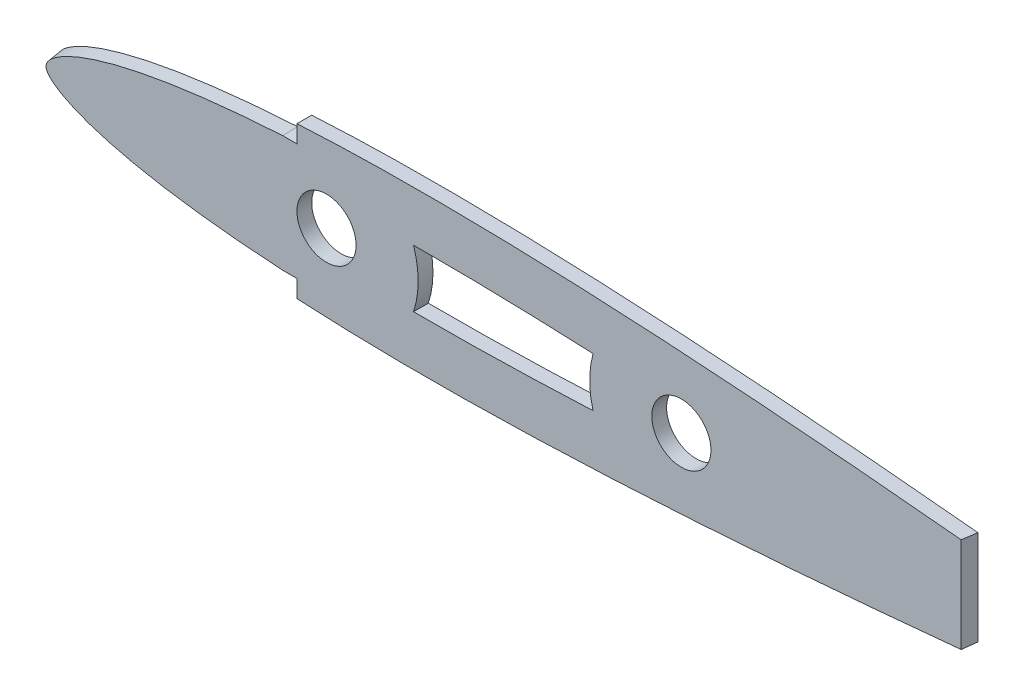
SolidWorks part; units mm, degrees
material "Balsa"
ref_plane "Front Plane" through (0, 0, 0) normal (0, 0, 1) x (1, 0, 0)
ref_plane "Top Plane" through (0, 0, 0) normal (0, 1, 0) x (1, 0, 0)
ref_plane "Right Plane" through (0, 0, 0) normal (1, 0, 0) x (0, 0, -1)
curve "Curve1"
  spline degree 3 poles (283.1769, -0.4783, 0) (283.1769, 0.4783, 0) (282.223, 0.3615, 0) (281.0143, 0.7018, 0) (278.7977, 0.9121, 0) (275.8116, 1.3634, 0) (271.9651, 1.8671, 0) (267.3264, 2.4878, 0) (261.9077, 3.1895, 0) (255.7482, 3.9707, 0) (248.8838, 4.8179, 0) (241.3575, 5.7194, 0) (233.2156, 6.6641, 0) (224.5081, 7.6392, 0) (215.289, 8.6327, 0) (205.6149, 9.6324, 0) (195.5456, 10.6252, 0) (185.1431, 11.5974, 0) (174.4716, 12.536, 0) (163.5969, 13.4255, 0) (152.5858, 14.2512, 0) (141.5064, 14.998, 0) (130.4269, 15.6501, 0) (119.4155, 16.1911, 0) (108.5401, 16.6066, 0) (97.8677, 16.883, 0) (87.464, 17.0069, 0) (77.3931, 16.9683, 0) (67.717, 16.7598, 0) (58.4953, 16.3762, 0) (49.7847, 15.8164, 0) (41.6389, 15.0822, 0) (34.1075, 14.1792, 0) (27.2365, 13.1151, 0) (21.0677, 11.9011, 0) (15.637, 10.5509, 0) (10.9755, 9.0777, 0) (7.1067, 7.4951, 0) (4.043, 5.8139, 0) (1.7891, 4.0308, 0) (0.3455, 2.1026, 0) (-0.161, 0, 0) (0.3455, -2.1026, 0) (1.7891, -4.0308, 0) (4.043, -5.8139, 0) (7.1067, -7.4951, 0) (10.9755, -9.0777, 0) (15.637, -10.5509, 0) (21.0677, -11.9011, 0) (27.2365, -13.1151, 0) (34.1075, -14.1792, 0) (41.6389, -15.0822, 0) (49.7847, -15.8164, 0) (58.4953, -16.3762, 0) (67.717, -16.7598, 0) (77.3931, -16.9683, 0) (87.464, -17.0069, 0) (97.8677, -16.883, 0) (108.5401, -16.6066, 0) (119.4155, -16.1911, 0) (130.4269, -15.6501, 0) (141.5064, -14.998, 0) (152.5858, -14.2512, 0) (163.5969, -13.4255, 0) (174.4716, -12.536, 0) (185.1431, -11.5974, 0) (195.5456, -10.6252, 0) (205.6149, -9.6324, 0) (215.289, -8.6327, 0) (224.5081, -7.6392, 0) (233.2156, -6.6641, 0) (241.3575, -5.7194, 0) (248.8838, -4.8179, 0) (255.7482, -3.9707, 0) (261.9077, -3.1895, 0) (267.3264, -2.4878, 0) (271.9651, -1.8671, 0) (275.8116, -1.3634, 0) (278.7977, -0.9121, 0) (281.0143, -0.7018, 0) (282.223, -0.3615, 0) (283.1769, -0.4783, 0) (283.1769, 0.4783, 0) (282.223, 0.3615, 0) knots -0.004279 -0.001997 -0.001234 0 0.000762 0.003045 0.006832 0.012101 0.018818 0.026939 0.036415 0.047185 0.05918 0.072328 0.086544 0.101741 0.117823 0.134691 0.15224 0.170361 0.188941 0.207865 0.227016 0.246276 0.265525 0.284645 0.30352 0.322035 0.340078 0.357543 0.374325 0.39033 0.405464 0.419644 0.432793 0.444844 0.455738 0.465429 0.473886 0.481102 0.487102 0.491975 0.495931 0.499383 0.502835 0.50679 0.511664 0.517664 0.524879 0.533337 0.543028 0.553922 0.565972 0.579122 0.593302 0.608436 0.62444 0.641223 0.658687 0.676731 0.695245 0.714121 0.733241 0.75249 0.77175 0.7909 0.809825 0.828404 0.846525 0.864074 0.880942 0.897025 0.912222 0.926438 0.939585 0.951581 0.962351 0.971826 0.979948 0.986664 0.991933 0.995721 0.998003 0.998766 1 1.000762 1.003045 1.006832 periodic
sketch "Sketch1" plane through (0, 0, 0) normal (0, 0, 1) x (1, 0, 0)
  spline S0 degree 3 poles (283.1769, -0.4783) (283.1769, 0.4783) (282.223, 0.3615) (281.0143, 0.7018) (278.7977, 0.9121) (275.8116, 1.3634) (271.9651, 1.8671) (267.3264, 2.4878) (261.9077, 3.1895) (255.7482, 3.9707) (248.8838, 4.8179) (241.3575, 5.7194) (233.2156, 6.6641) (224.5081, 7.6392) (215.289, 8.6327) (205.6149, 9.6324) (195.5456, 10.6252) (185.1431, 11.5974) (174.4716, 12.536) (163.5969, 13.4255) (152.5858, 14.2512) (141.5064, 14.998) (130.4269, 15.6501) (119.4155, 16.1911) (108.5401, 16.6066) (97.8677, 16.883) (87.464, 17.0069) (77.3931, 16.9683) (67.717, 16.7598) (58.4953, 16.3762) (49.7847, 15.8164) (41.6389, 15.0822) (34.1075, 14.1792) (27.2365, 13.1151) (21.0677, 11.9011) (15.637, 10.5509) (10.9755, 9.0777) (7.1067, 7.4951) (4.043, 5.8139) (1.7891, 4.0308) (0.3455, 2.1026) (-0.161, 0) (0.3455, -2.1026) (1.7891, -4.0308) (4.043, -5.8139) (7.1067, -7.4951) (10.9755, -9.0777) (15.637, -10.5509) (21.0677, -11.9011) (27.2365, -13.1151) (34.1075, -14.1792) (41.6389, -15.0822) (49.7847, -15.8164) (58.4953, -16.3762) (67.717, -16.7598) (77.3931, -16.9683) (87.464, -17.0069) (97.8677, -16.883) (108.5401, -16.6066) (119.4155, -16.1911) (130.4269, -15.6501) (141.5064, -14.998) (152.5858, -14.2512) (163.5969, -13.4255) (174.4716, -12.536) (185.1431, -11.5974) (195.5456, -10.6252) (205.6149, -9.6324) (215.289, -8.6327) (224.5081, -7.6392) (233.2156, -6.6641) (241.3575, -5.7194) (248.8838, -4.8179) (255.7482, -3.9707) (261.9077, -3.1895) (267.3264, -2.4878) (271.9651, -1.8671) (275.8116, -1.3634) (278.7977, -0.9121) (281.0143, -0.7018) (282.223, -0.3615) (283.1769, -0.4783) (283.1769, 0.4783) (282.223, 0.3615) knots -0.004279 -0.001997 -0.001234 0 0.000762 0.003045 0.006832 0.012101 0.018818 0.026939 0.036415 0.047185 0.05918 0.072328 0.086544 0.101741 0.117823 0.134691 0.15224 0.170361 0.188941 0.207865 0.227016 0.246276 0.265525 0.284645 0.30352 0.322035 0.340078 0.357543 0.374325 0.39033 0.405464 0.419644 0.432793 0.444844 0.455738 0.465429 0.473886 0.481102 0.487102 0.491975 0.495931 0.499383 0.502835 0.50679 0.511664 0.517664 0.524879 0.533337 0.543028 0.553922 0.565972 0.579122 0.593302 0.608436 0.62444 0.641223 0.658687 0.676731 0.695245 0.714121 0.733241 0.75249 0.77175 0.7909 0.809825 0.828404 0.846525 0.864074 0.880942 0.897025 0.912222 0.926438 0.939585 0.951581 0.962351 0.971826 0.979948 0.986664 0.991933 0.995721 0.998003 0.998766 1 1.000762 1.003045 1.006832 only from (283.0068, 0.3566) to (283.0068, 0.3566) construction
  spline S1 degree 3 poles (283.1769, -0.4783) (283.1769, 0.4783) (282.223, 0.3615) (281.0143, 0.7018) (278.7977, 0.9121) (275.8116, 1.3634) (271.9651, 1.8671) (267.3264, 2.4878) (261.9077, 3.1895) (255.7482, 3.9707) (248.8838, 4.8179) (241.3575, 5.7194) (233.2156, 6.6641) (224.5081, 7.6392) (215.289, 8.6327) (205.6149, 9.6324) (195.5456, 10.6252) (185.1431, 11.5974) (174.4716, 12.536) (163.5969, 13.4255) (152.5858, 14.2512) (141.5064, 14.998) (130.4269, 15.6501) (119.4155, 16.1911) (108.5401, 16.6066) (97.8677, 16.883) (87.464, 17.0069) (77.3931, 16.9683) (67.717, 16.7598) (58.4953, 16.3762) (49.7847, 15.8164) (41.6389, 15.0822) (34.1075, 14.1792) (27.2365, 13.1151) (21.0677, 11.9011) (15.637, 10.5509) (10.9755, 9.0777) (7.1067, 7.4951) (4.043, 5.8139) (1.7891, 4.0308) (0.3455, 2.1026) (-0.161, 0) (0.3455, -2.1026) (1.7891, -4.0308) (4.043, -5.8139) (7.1067, -7.4951) (10.9755, -9.0777) (15.637, -10.5509) (21.0677, -11.9011) (27.2365, -13.1151) (34.1075, -14.1792) (41.6389, -15.0822) (49.7847, -15.8164) (58.4953, -16.3762) (67.717, -16.7598) (77.3931, -16.9683) (87.464, -17.0069) (97.8677, -16.883) (108.5401, -16.6066) (119.4155, -16.1911) (130.4269, -15.6501) (141.5064, -14.998) (152.5858, -14.2512) (163.5969, -13.4255) (174.4716, -12.536) (185.1431, -11.5974) (195.5456, -10.6252) (205.6149, -9.6324) (215.289, -8.6327) (224.5081, -7.6392) (233.2156, -6.6641) (241.3575, -5.7194) (248.8838, -4.8179) (255.7482, -3.9707) (261.9077, -3.1895) (267.3264, -2.4878) (271.9651, -1.8671) (275.8116, -1.3634) (278.7977, -0.9121) (281.0143, -0.7018) (282.223, -0.3615) (283.1769, -0.4783) (283.1769, 0.4783) (282.223, 0.3615) knots -0.004279 -0.001997 -0.001234 0 0.000762 0.003045 0.006832 0.012101 0.018818 0.026939 0.036415 0.047185 0.05918 0.072328 0.086544 0.101741 0.117823 0.134691 0.15224 0.170361 0.188941 0.207865 0.227016 0.246276 0.265525 0.284645 0.30352 0.322035 0.340078 0.357543 0.374325 0.39033 0.405464 0.419644 0.432793 0.444844 0.455738 0.465429 0.473886 0.481102 0.487102 0.491975 0.495931 0.499383 0.502835 0.50679 0.511664 0.517664 0.524879 0.533337 0.543028 0.553922 0.565972 0.579122 0.593302 0.608436 0.62444 0.641223 0.658687 0.676731 0.695245 0.714121 0.733241 0.75249 0.77175 0.7909 0.809825 0.828404 0.846525 0.864074 0.880942 0.897025 0.912222 0.926438 0.939585 0.951581 0.962351 0.971826 0.979948 0.986664 0.991933 0.995721 0.998003 0.998766 1 1.000762 1.003045 1.006832 only from (283.0068, 0.3566) to (283.0068, 0.3566)
extrude "Boss-Extrude1" add sketch "Sketch1" along normal blind 3.175
sketch "Sketch2" plane through (0, 0, 3.175) normal (0, 0, 1) x (1, 0, 0)
  circle A0 centre (63.5, 0) radius 6.35
  circle A1 centre (139.7, 0) radius 6.35
  dimension "D1" = 12.7
  dimension "D2" = 12.7
  dimension "D3" = 0
  dimension "D4" = 0
  dimension "D5" = 63.5
  dimension "D6" = 139.7
extrude "Cut-Extrude1" cut sketch "Sketch2" against normal blind 3.175
sketch "Sketch3" plane through (0, 0, 0) normal (0, 1, 0) x (1, 0, 0)
  line L2 (200.2201, 0) -> (199.7735, -3.175)
  line L8 (283.1344, -3.175) -> (283.1344, 0) construction
  line L9 (283.1344, -3.175) -> (283.1344, 0)
  line L10 (199.7735, -3.175) -> (283.1344, -3.175)
extrude "Cut-Extrude2" cut sketch "Sketch3" against normal through all both and the other way through all
sketch "Sketch4" plane through (0, 0, 0) normal (0, 0, -1) x (-1, 0, 0)
  line L0 (-57.15, -15.9311) -> (-57.15, -12.6144)
  line L1 (-57.15, -15.9311) -> (-57.15, -12.6144)
  line L2 (-54.102, -12.6144) -> (-57.15, -12.6144)
  line L3 (-54.102, -12.6144) -> (-57.15, -12.6144)
  line L4 (-57.15, 12.6144) -> (-57.15, 15.9311)
  line L5 (-57.15, 12.6144) -> (-57.15, 15.9311)
  line L6 (-57.15, 12.6144) -> (-54.102, 12.6144)
  line L7 (-57.15, 12.6144) -> (-54.102, 12.6144)
  line L9 (16.291, 29.4613) -> (3.1074, -36.0979)
  line L11 (-57.15, -15.9311) -> (-57.15, -26.911)
  line L12 (-57.15, -26.911) -> (3.1074, -36.0979)
  line L13 (-57.15, 15.9311) -> (-57.15, 23.7689)
  line L14 (-57.15, 23.7689) -> (16.291, 29.4613)
  spline S0 degree 3 poles (1603.9477, 1127.4313) (-409.4491, -100.2252) (-222.7052, 25.2394) (-46.8504, 12.1195) (-43.234, 11.8063) (-39.6271, 11.4462) (-36.0313, 11.0349) (-32.4506, 10.5661) (-28.886, 10.0331) (-25.9367, 9.528) (-23.5902, 9.0821) (-21.8403, 8.725) (-20.101, 8.3428) (-18.3748, 7.9334) (-16.663, 7.4946) (-14.9702, 7.0233) (-13.3008, 6.5163) (-11.6611, 5.9687) (-10.0604, 5.3771) (-8.5083, 4.731) (-7.0229, 4.0237) (-5.6385, 3.2547) (-4.6091, 2.5577) (-3.9035, 1.9678) (-3.4556, 1.5205) (-3.0957, 1.0697) (-2.8713, 0.6793) (-2.7459, 0.308) (-2.7091, 0) (-2.7459, -0.308) (-2.8713, -0.6793) (-3.0958, -1.0697) (-3.4556, -1.5205) (-3.9035, -1.9678) (-4.6094, -2.5579) (-5.6383, -3.2546) (-7.023, -4.0238) (-8.5083, -4.731) (-10.0604, -5.3771) (-11.6611, -5.9687) (-13.3008, -6.5163) (-14.9701, -7.0232) (-16.663, -7.4946) (-18.3748, -7.9334) (-20.101, -8.3428) (-21.8403, -8.725) (-23.5902, -9.0821) (-25.9368, -9.528) (-28.8859, -10.0331) (-32.4506, -10.5661) (-36.0313, -11.0349) (-39.6271, -11.4462) (-43.234, -11.8063) (-46.8504, -12.1195) (-222.1359, -25.197) (-408.2838, 99.3983) (1617.0872, -1107.8528) knots -4.455305 -4.455305 -4.455305 -4.455305 0.03125 0.0625 0.09375 0.125 0.15625 0.1875 0.21875 0.25 0.265625 0.28125 0.296875 0.3125 0.328125 0.34375 0.359375 0.375 0.390625 0.40625 0.421875 0.4375 0.453125 0.460938 0.46875 0.476562 0.484375 0.492188 0.5 0.507812 0.515625 0.523438 0.53125 0.539062 0.546875 0.5625 0.578125 0.59375 0.609375 0.625 0.640625 0.65625 0.671875 0.6875 0.703125 0.71875 0.734375 0.75 0.78125 0.8125 0.84375 0.875 0.90625 0.9375 0.96875 5.440565 5.440565 5.440565 5.440565 only from (-54.102, 12.6144) to (-54.102, -12.6144)
  spline S1 degree 3 poles (-54.102, 12.6144) (-52.893, 12.5437) (-50.4746, 12.3899) (-46.8504, 12.1195) (-43.234, 11.8063) (-39.6271, 11.4462) (-36.0313, 11.0349) (-32.4506, 10.5661) (-28.886, 10.0331) (-25.9367, 9.528) (-23.5902, 9.0821) (-21.8403, 8.725) (-20.101, 8.3428) (-18.3748, 7.9334) (-16.663, 7.4946) (-14.9702, 7.0233) (-13.3008, 6.5163) (-11.6611, 5.9687) (-10.0604, 5.3771) (-8.5083, 4.731) (-7.0229, 4.0237) (-5.6385, 3.2547) (-4.6091, 2.5577) (-3.9035, 1.9678) (-3.4556, 1.5205) (-3.0957, 1.0697) (-2.8713, 0.6793) (-2.7459, 0.308) (-2.7091, 0) (-2.7459, -0.308) (-2.8713, -0.6793) (-3.0958, -1.0697) (-3.4556, -1.5205) (-3.9035, -1.9678) (-4.6094, -2.5579) (-5.6383, -3.2546) (-7.023, -4.0238) (-8.5083, -4.731) (-10.0604, -5.3771) (-11.6611, -5.9687) (-13.3008, -6.5163) (-14.9701, -7.0232) (-16.663, -7.4946) (-18.3748, -7.9334) (-20.101, -8.3428) (-21.8403, -8.725) (-23.5902, -9.0821) (-25.9368, -9.528) (-28.8859, -10.0331) (-32.4506, -10.5661) (-36.0313, -11.0349) (-39.6271, -11.4462) (-43.234, -11.8063) (-46.8504, -12.1195) (-50.4745, -12.3899) (-52.893, -12.5437) (-54.102, -12.6144) knots 0 0 0 0 0.03125 0.0625 0.09375 0.125 0.15625 0.1875 0.21875 0.25 0.265625 0.28125 0.296875 0.3125 0.328125 0.34375 0.359375 0.375 0.390625 0.40625 0.421875 0.4375 0.453125 0.460938 0.46875 0.476562 0.484375 0.492188 0.5 0.507812 0.515625 0.523438 0.53125 0.539062 0.546875 0.5625 0.578125 0.59375 0.609375 0.625 0.640625 0.65625 0.671875 0.6875 0.703125 0.71875 0.734375 0.75 0.78125 0.8125 0.84375 0.875 0.90625 0.9375 0.96875 1 1 1 1
sketch "Sketch5" plane through (0, 0, 3.175) normal (0, 0, 1) x (1, 0, 0)
  line L0 (57.15, -15.8407) -> (57.15, -12.5178)
  line L1 (57.15, -15.8407) -> (57.15, -12.5178)
  line L2 (54.102, -12.5178) -> (57.15, -12.5178)
  line L3 (54.102, -12.5178) -> (57.15, -12.5178)
  line L4 (57.15, 12.5178) -> (57.15, 15.8407)
  line L5 (57.15, 12.5178) -> (57.15, 15.8407)
  line L6 (57.15, 12.5178) -> (54.102, 12.5178)
  line L7 (57.15, 12.5178) -> (54.102, 12.5178)
  line L9 (-13.6603, 32.1968) -> (4.7514, -35.9264)
  line L11 (57.15, 15.8407) -> (57.15, 24.5287)
  line L12 (57.15, 24.5287) -> (-13.6603, 32.1968)
  line L13 (57.15, -15.8407) -> (57.15, -29.0129)
  line L14 (57.15, -29.0129) -> (4.7514, -35.9264)
  spline S0 degree 3 poles (-1613.5734, 1113.0651) (405.921, -99.1234) (220.9953, 25.1428) (46.923, 12.0225) (43.3429, 11.7096) (39.7723, 11.3502) (36.213, 10.9401) (32.6687, 10.4731) (29.1406, 9.9424) (26.2217, 9.4398) (23.8996, 8.9963) (22.1681, 8.6412) (20.4471, 8.2613) (18.7392, 7.8544) (17.0458, 7.4185) (15.3713, 6.9503) (13.7204, 6.447) (12.0991, 5.9036) (10.5167, 5.3168) (8.9829, 4.6764) (7.5154, 3.9756) (6.1484, 3.2144) (5.1324, 2.5254) (4.4363, 1.9426) (3.9945, 1.5009) (3.6396, 1.0557) (3.4182, 0.6703) (3.2945, 0.3038) (3.2583, 0) (3.2945, -0.3038) (3.4182, -0.6703) (3.6396, -1.0557) (3.9945, -1.5009) (4.4363, -1.9426) (5.1328, -2.5256) (6.1482, -3.2142) (7.5155, -3.9757) (8.9829, -4.6763) (10.5168, -5.3169) (12.0991, -5.9036) (13.7204, -6.447) (15.3713, -6.9503) (17.0458, -7.4185) (18.7392, -7.8544) (20.4471, -8.2613) (22.1681, -8.6412) (23.8996, -8.9963) (26.2218, -9.4398) (29.1405, -9.9424) (32.6687, -10.4731) (36.2129, -10.9401) (39.7723, -11.3502) (43.3429, -11.7096) (46.923, -12.0225) (220.4075, -25.0986) (404.7164, 98.2692) (-1626.8557, -1092.8409) knots -4.454752 -4.454752 -4.454752 -4.454752 0.03125 0.0625 0.09375 0.125 0.15625 0.1875 0.21875 0.25 0.265625 0.28125 0.296875 0.3125 0.328125 0.34375 0.359375 0.375 0.390625 0.40625 0.421875 0.4375 0.453125 0.460938 0.46875 0.476562 0.484375 0.492188 0.5 0.507812 0.515625 0.523438 0.53125 0.539062 0.546875 0.5625 0.578125 0.59375 0.609375 0.625 0.640625 0.65625 0.671875 0.6875 0.703125 0.71875 0.734375 0.75 0.78125 0.8125 0.84375 0.875 0.90625 0.9375 0.96875 5.439378 5.439378 5.439378 5.439378 only from (54.102, 12.5178) to (54.102, -12.5178)
  spline S1 degree 3 poles (54.102, 12.5178) (52.9051, 12.4469) (50.5109, 12.2929) (46.923, 12.0225) (43.3429, 11.7096) (39.7723, 11.3502) (36.213, 10.9401) (32.6687, 10.4731) (29.1406, 9.9424) (26.2217, 9.4398) (23.8996, 8.9963) (22.1681, 8.6412) (20.4471, 8.2613) (18.7392, 7.8544) (17.0458, 7.4185) (15.3713, 6.9503) (13.7204, 6.447) (12.0991, 5.9036) (10.5167, 5.3168) (8.9829, 4.6764) (7.5154, 3.9756) (6.1484, 3.2144) (5.1324, 2.5254) (4.4363, 1.9426) (3.9945, 1.5009) (3.6396, 1.0557) (3.4182, 0.6703) (3.2945, 0.3038) (3.2583, 0) (3.2945, -0.3038) (3.4182, -0.6703) (3.6396, -1.0557) (3.9945, -1.5009) (4.4363, -1.9426) (5.1328, -2.5256) (6.1482, -3.2142) (7.5155, -3.9757) (8.9829, -4.6763) (10.5168, -5.3169) (12.0991, -5.9036) (13.7204, -6.447) (15.3713, -6.9503) (17.0458, -7.4185) (18.7392, -7.8544) (20.4471, -8.2613) (22.1681, -8.6412) (23.8996, -8.9963) (26.2218, -9.4398) (29.1405, -9.9424) (32.6687, -10.4731) (36.2129, -10.9401) (39.7723, -11.3502) (43.3429, -11.7096) (46.923, -12.0225) (50.5109, -12.2929) (52.9051, -12.4469) (54.102, -12.5178) knots 0 0 0 0 0.03125 0.0625 0.09375 0.125 0.15625 0.1875 0.21875 0.25 0.265625 0.28125 0.296875 0.3125 0.328125 0.34375 0.359375 0.375 0.390625 0.40625 0.421875 0.4375 0.453125 0.460938 0.46875 0.476562 0.484375 0.492188 0.5 0.507812 0.515625 0.523438 0.53125 0.539062 0.546875 0.5625 0.578125 0.59375 0.609375 0.625 0.640625 0.65625 0.671875 0.6875 0.703125 0.71875 0.734375 0.75 0.78125 0.8125 0.84375 0.875 0.90625 0.9375 0.96875 1 1 1 1
loft "Cut-Loft1" cut profiles "Sketch5", "Sketch4" connector at (-13.6603, 32.1968, 3.175) connector at (-16.291, 29.4613, 0)
sketch "Sketch6" plane through (0, 0, 0) normal (0, 0, -1) x (-1, 0, 0)
  arc A4 (-120.7437, -5.3063) -> (-120.7437, 5.3063) centre (-139.7, 0) ccw
  arc A6 (-82.1883, 6.1845) -> (-82.1883, -6.1845) centre (-63.5, 0) ccw
  spline S5 degree 3 poles (-120.7437, 5.3063) (-116.114, 5.5168) (-111.4868, 5.6956) (-101.374, 6.0042) (-95.8907, 6.1186) (-87.6714, 6.1897) (-84.9282, 6.1967) (-82.1883, 6.1845) knots 0.519742 0.519742 0.519742 0.519742 0.625 0.625 0.75 0.75 0.812699 0.812699 0.812699 0.812699
  spline S9 degree 3 poles (-82.1883, -6.1845) (-84.9282, -6.1967) (-87.6714, -6.1897) (-95.8907, -6.1186) (-101.374, -6.0042) (-111.4868, -5.6956) (-116.114, -5.5168) (-120.7437, -5.3063) knots 0.187301 0.187301 0.187301 0.187301 0.25 0.25 0.375 0.375 0.480258 0.480258 0.480258 0.480258
extrude "Cut-Extrude3" cut sketch "Sketch6" against normal blind 7.62
